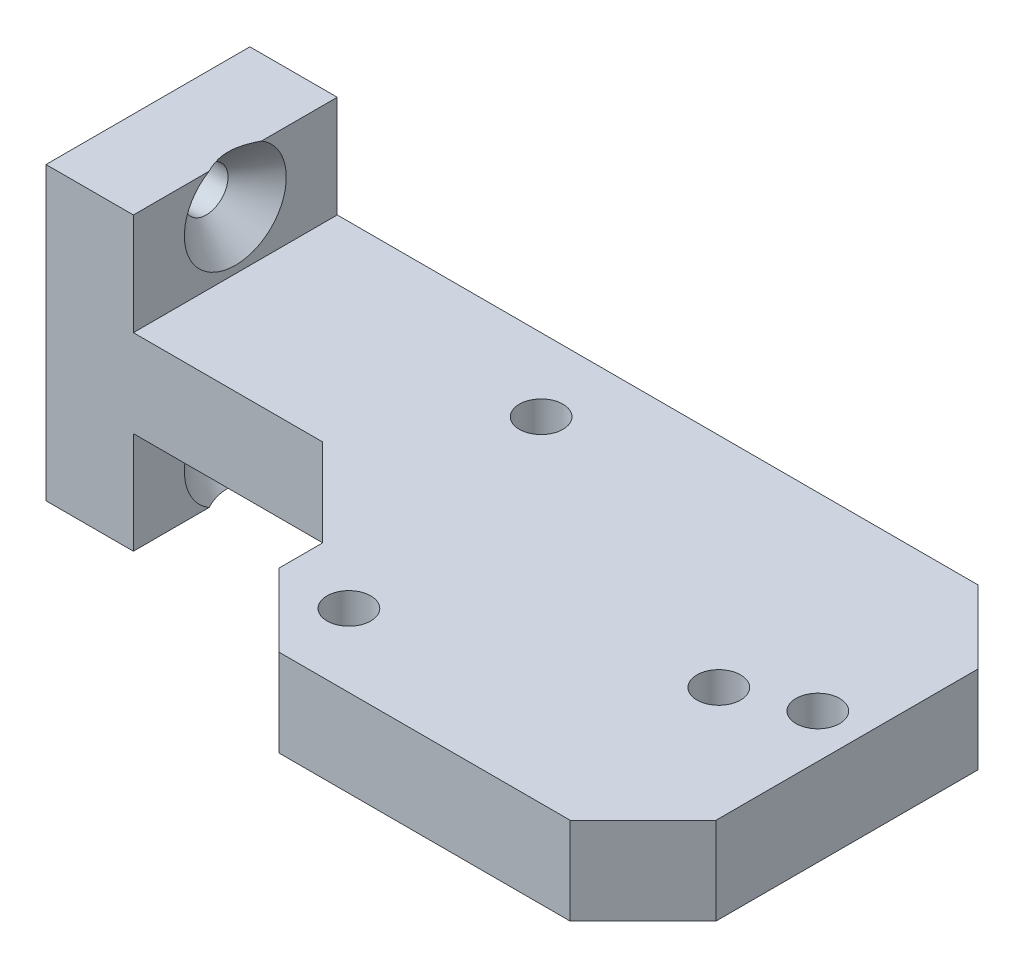
SolidWorks part; units mm, degrees
material "1350 合金"
ref_plane "前视基准面" through (0, 0, 0) normal (0, 0, 1) x (1, 0, 0)
ref_plane "上视基准面" through (0, 0, 0) normal (0, 1, 0) x (1, 0, 0)
ref_plane "右视基准面" through (0, 0, 0) normal (1, 0, 0) x (0, 0, -1)
sketch "草图1" plane through (0, 0, 0) normal (0, 1, 0) x (1, 0, 0)
  line L0 (0, 14) -> (0, 0)
  line L1 (0, 0) -> (25, 0)
  line L2 (25, 0) -> (25, -14)
  line L3 (25, -14) -> (55, -14)
  line L4 (55, -14) -> (55, 14)
  line L5 (55, 14) -> (0, 14)
  line L8 (40, -14) -> (40, 14.122) construction
  circle A0 centre (25, 9) radius 1.5
  circle A1 centre (52, 1) radius 1.5
  circle A2 centre (29.8, -9) radius 1.5
  circle A3 centre (47.2, -1) radius 1.5
  point P8 (20, 14.122)
  point P15 (0, 0)
  point P20 (35, 16.3412)
  point P21 (0, 0)
  point P22 (0, 0)
  point P23 (20, 14.122)
  point P24 (0.5706, 14)
  dimension "D9" = 3
  dimension "D1" = 14
  dimension "D2" = 15
  dimension "D3" = 14
  dimension "D4" = 25
  dimension "D5" = 30
  dimension "D6" = 22.2
  dimension "D7" = 10
  dimension "D8" = 22.2
  dimension "D10" = 5
  dimension "D12" = 10
  dimension "D13" = 3
  dimension "D14" = 13
extrude "凸台-拉伸1" add sketch "草图1" along normal mid plane 6
sketch "草图2" plane through (0, 0, 0) normal (1, 0, 0) x (0, 0, -1)
  line L1 (14, 10) -> (0, 10)
  line L2 (14, 10) -> (14, -10)
  line L3 (14, -10) -> (0, -10)
  line L4 (0, 10) -> (0, -10)
  line L5 (7, 7) -> (7, -7) construction
  line L6 (14, 3) -> (14, -3) construction
  circle A0 centre (7, 7) radius 1.5
  circle A1 centre (7, -7) radius 1.5
  point P4 (0, 0)
  point P12 (7, 10)
  point P13 (7, 0)
  dimension "D2" = 3
  dimension "D1" = 20
  dimension "D3" = 14
extrude "凸台-拉伸2" add sketch "草图2" along normal blind 6
chamfer "倒角1" distance 2 angle 45 2 edges at (6, -7, -8.5) (6, 7, -8.5)
chamfer "倒角2" distance 6 angle 45 1 edges at (25, 0, 0)
chamfer "倒角3" distance 5 angle 45 3 edges at (55, 0, 14) (25, 0, 14) (55, 0, -14)
